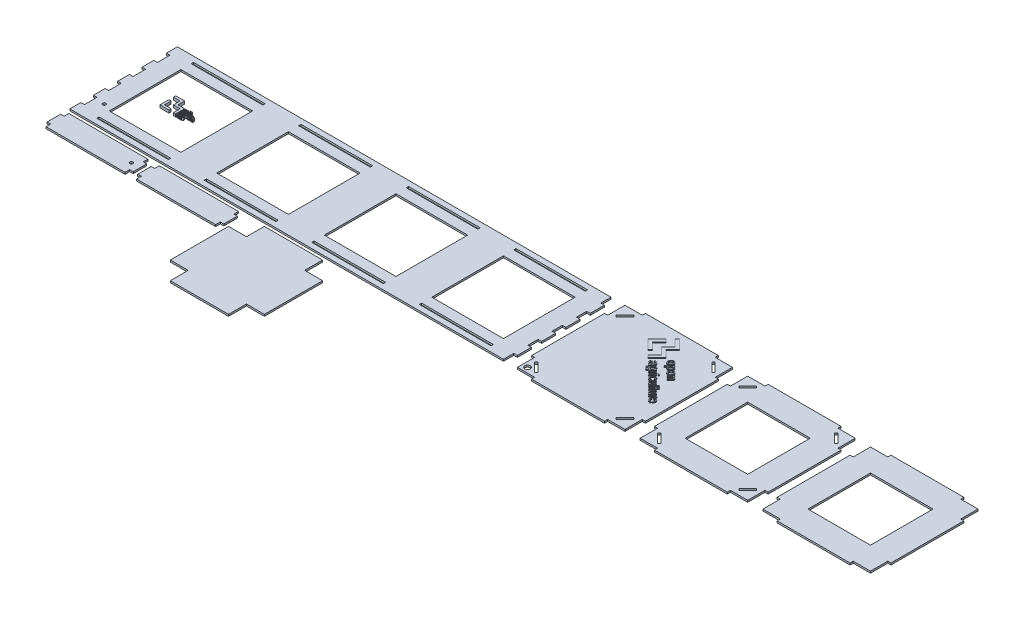
SolidWorks part; units mm, degrees
ref_plane "Front" through (0, 0, 0) normal (0, 0, 1) x (1, 0, 0)
ref_plane "Top" through (0, 0, 0) normal (0, 1, 0) x (1, 0, 0)
ref_plane "Right" through (0, 0, 0) normal (1, 0, 0) x (0, 0, -1)
sketch "Sketch1" plane through (0, 0, 0) normal (0, 1, 0) x (1, 0, 0)
  line L0 (0, 0) -> (228.6, 0) construction
  line L2 (-76.2, 76.2) -> (-76.2, -76.2) construction
  line L4 (76.2, 76.2) -> (76.2, -76.2) construction
  line L5 (-76.2, 76.2) -> (76.2, -76.2) construction
  line L6 (-76.2, -76.2) -> (76.2, 76.2) construction
  line L11 (76.2, 76.2) -> (228.6, 76.2)
  line L12 (76.2, 76.2) -> (76.2, -76.2) construction
  line L13 (76.2, -76.2) -> (228.6, -76.2)
  line L14 (228.6, 76.2) -> (228.6, -76.2) construction
  line L19 (-76.2, -76.2) -> (-228.6, -76.2)
  line L20 (-76.2, -76.2) -> (-76.2, 76.2) construction
  line L21 (-76.2, 76.2) -> (-228.6, 76.2)
  line L28 (76.2, -76.2) -> (-76.2, -76.2)
  line L34 (76.2, 76.2) -> (-76.2, 76.2)
  line L35 (-228.6, 76.2) -> (-228.6, -76.2) construction
  line L43 (-228.6, 76.2) -> (-381, 76.2)
  line L44 (-381, 76.2) -> (-381, -76.2) construction
  line L45 (-381, -76.2) -> (-228.6, -76.2)
  line L46 (228.6, 76.2) -> (228.6, 61.6712)
  line L47 (228.6, 61.6712) -> (233.68, 61.6712)
  line L48 (233.68, 61.6712) -> (233.68, 41.7322)
  line L49 (233.68, 41.7322) -> (228.6, 41.7322)
  line L50 (228.6, 41.7322) -> (228.6, 27.2034)
  line L51 (228.6, 27.2034) -> (233.68, 27.2034)
  line L63 (233.68, 27.2034) -> (233.68, 7.2644)
  line L64 (233.68, 7.2644) -> (228.6, 7.2644)
  line L65 (228.6, 7.2644) -> (228.6, -7.2644)
  line L66 (228.6, -7.2644) -> (233.68, -7.2644)
  line L67 (233.68, -7.2644) -> (233.68, -27.2034)
  line L68 (233.68, -27.2034) -> (228.6, -27.2034)
  line L69 (228.6, -27.2034) -> (228.6, -41.7322)
  line L70 (228.6, -41.7322) -> (233.68, -41.7322)
  line L71 (233.68, -41.7322) -> (233.68, -61.6712)
  line L72 (233.68, -61.6712) -> (228.6, -61.6712)
  line L73 (228.6, -61.6712) -> (228.6, -76.2)
  line L74 (-381, 76.2) -> (-386.08, 76.2)
  line L76 (-386.08, 60.5917) -> (-381, 60.5917)
  line L78 (-381, 42.8117) -> (-386.08, 42.8117)
  line L80 (-386.08, 26.1239) -> (-381, 26.1239)
  line L82 (-381, 8.3439) -> (-386.08, 8.3439)
  line L84 (-386.08, -8.3439) -> (-381, -8.3439)
  line L86 (-381, -26.1239) -> (-386.08, -26.1239)
  line L88 (-386.08, -42.8117) -> (-381, -42.8117)
  line L90 (-381, -60.5917) -> (-386.08, -60.5917)
  line L92 (-386.08, -76.2) -> (-381, -76.2)
  line L93 (233.68, 17.2339) -> (-381, 17.2339) construction
  line L94 (-381, 51.7017) -> (233.68, 51.7017) construction
  line L95 (-386.08, 76.2) -> (-386.08, 60.5917)
  line L96 (-386.08, 42.8117) -> (-386.08, 26.1239)
  line L97 (-381, 60.5917) -> (-381, 42.8117)
  line L98 (-381, 26.1239) -> (-381, 8.3439)
  line L99 (-381, -8.3439) -> (-381, -26.1239)
  line L100 (-381, -42.8117) -> (-381, -60.5917)
  line L101 (-381, -51.7017) -> (233.68, -51.7017) construction
  line L102 (-381, -17.2339) -> (233.68, -17.2339) construction
  line L103 (-386.08, 8.3439) -> (-386.08, -8.3439)
  line L104 (-386.08, -26.1239) -> (-386.08, -42.8117)
  line L105 (-386.08, -60.5917) -> (-386.08, -76.2)
  point P0 (0, 0)
  dimension "D1" = 152.4
  dimension "D2" = 152.4
  dimension "D3" = 5.08
  dimension "D4" = 19.939
  dimension "D5" = 17.78
extrude "Boss-Extrude1" add sketch "Sketch1" along normal blind 2.54
sketch "Sketch4" plane through (0, 2.54, 0) normal (0, 1, 0) x (1, 0, 0)
  line L0 (-228.6, 76.2) -> (-228.6, -76.2) construction
  line L1 (-228.6, 76.2) -> (-228.6, -76.2)
  line L2 (-76.2, 76.2) -> (-76.2, -76.2) construction
  line L3 (-76.2, 76.2) -> (-76.2, -76.2)
  line L4 (76.2, 76.2) -> (76.2, -76.2) construction
  line L5 (76.2, 76.2) -> (76.2, -76.2)
sketch "Sketch5" plane through (0, 2.54, 0) normal (0, 1, 0) x (1, 0, 0)
  line L0 (-381, -8.3439) -> (-381, 8.3439) construction
  line L1 (-228.6, 0) -> (-381, 0) construction
  line L2 (-228.6, 76.2) -> (-228.6, -76.2) construction
  line L3 (-228.6, 0) -> (-76.2, 0) construction
  line L4 (-76.2, 76.2) -> (-76.2, -76.2) construction
  line L5 (-76.2, 0) -> (76.2, 0) construction
  line L6 (76.2, 76.2) -> (76.2, -76.2) construction
  line L7 (76.2, 0) -> (228.6, 0) construction
  line L8 (228.6, -7.2644) -> (228.6, 7.2644) construction
  line L9 (-304.8, 0) -> (-304.8, -76.2) construction
  line L10 (-386.08, -76.2) -> (228.6, -76.2) construction
  line L11 (-152.4, 0) -> (-152.4, -76.2) construction
  line L12 (0, 0) -> (0, -76.2) construction
  line L13 (152.4, 0) -> (152.4, -76.2) construction
  line L14 (-254, -68.58) -> (-254, -76.2) construction
  line L15 (-355.6, -65.278) -> (-254, -65.278)
  line L16 (-355.6, -65.278) -> (-355.6, -68.58)
  line L17 (-355.6, -68.58) -> (-254, -68.58)
  line L18 (-254, -65.278) -> (-254, -68.58)
  line L19 (-355.6, -65.278) -> (-254, -68.58) construction
  line L20 (-355.6, -68.58) -> (-254, -65.278) construction
  line L21 (-203.2, -65.278) -> (-101.6, -65.278)
  line L22 (-203.2, -65.278) -> (-203.2, -68.58)
  line L23 (-203.2, -68.58) -> (-101.6, -68.58)
  line L24 (-101.6, -65.278) -> (-101.6, -68.58)
  line L25 (-203.2, -65.278) -> (-101.6, -68.58) construction
  line L26 (-203.2, -68.58) -> (-101.6, -65.278) construction
  line L27 (-50.8, -68.58) -> (50.8, -68.58)
  line L28 (-50.8, -68.58) -> (-50.8, -65.278)
  line L29 (-50.8, -65.278) -> (50.8, -65.278)
  line L30 (50.8, -68.58) -> (50.8, -65.278)
  line L31 (-50.8, -68.58) -> (50.8, -65.278) construction
  line L32 (-50.8, -65.278) -> (50.8, -68.58) construction
  line L33 (101.6, -68.58) -> (203.2, -68.58)
  line L34 (101.6, -68.58) -> (101.6, -65.278)
  line L35 (101.6, -65.278) -> (203.2, -65.278)
  line L36 (203.2, -68.58) -> (203.2, -65.278)
  line L37 (101.6, -68.58) -> (203.2, -65.278) construction
  line L38 (101.6, -65.278) -> (203.2, -68.58) construction
  line L39 (101.6, 65.278) -> (203.2, 68.58) construction
  line L40 (101.6, 68.58) -> (203.2, 65.278) construction
  line L41 (-50.8, 65.278) -> (50.8, 68.58) construction
  line L42 (-50.8, 68.58) -> (50.8, 65.278) construction
  line L43 (-203.2, 68.58) -> (-101.6, 65.278) construction
  line L44 (-203.2, 65.278) -> (-101.6, 68.58) construction
  line L45 (-355.6, 68.58) -> (-254, 65.278) construction
  line L46 (-355.6, 65.278) -> (-254, 68.58) construction
  line L47 (-254, 68.58) -> (-254, 76.2) construction
  line L48 (203.2, 68.58) -> (203.2, 65.278)
  line L49 (101.6, 65.278) -> (203.2, 65.278)
  line L50 (101.6, 68.58) -> (101.6, 65.278)
  line L51 (101.6, 68.58) -> (203.2, 68.58)
  line L52 (50.8, 68.58) -> (50.8, 65.278)
  line L53 (-50.8, 65.278) -> (50.8, 65.278)
  line L54 (-50.8, 68.58) -> (-50.8, 65.278)
  line L55 (-50.8, 68.58) -> (50.8, 68.58)
  line L56 (-101.6, 65.278) -> (-101.6, 68.58)
  line L57 (-203.2, 68.58) -> (-101.6, 68.58)
  line L58 (-203.2, 65.278) -> (-203.2, 68.58)
  line L59 (-203.2, 65.278) -> (-101.6, 65.278)
  line L60 (-254, 65.278) -> (-254, 68.58)
  line L61 (-355.6, 68.58) -> (-254, 68.58)
  line L62 (-355.6, 65.278) -> (-355.6, 68.58)
  line L63 (-355.6, 65.278) -> (-254, 65.278)
  line L65 (-355.6, 50.8) -> (-254, 50.8)
  line L66 (-355.6, 50.8) -> (-355.6, -50.8)
  line L67 (-355.6, -50.8) -> (-254, -50.8)
  line L68 (-254, 50.8) -> (-254, -50.8)
  line L69 (-355.6, 50.8) -> (-254, -50.8) construction
  line L70 (-355.6, -50.8) -> (-254, 50.8) construction
  line L71 (-203.2, 50.8) -> (-101.6, 50.8)
  line L72 (-203.2, 50.8) -> (-203.2, -50.8)
  line L73 (-203.2, -50.8) -> (-101.6, -50.8)
  line L74 (-101.6, 50.8) -> (-101.6, -50.8)
  line L75 (-203.2, 50.8) -> (-101.6, -50.8) construction
  line L76 (-203.2, -50.8) -> (-101.6, 50.8) construction
  line L77 (-50.8, 50.8) -> (50.8, 50.8)
  line L78 (-50.8, 50.8) -> (-50.8, -50.8)
  line L79 (-50.8, -50.8) -> (50.8, -50.8)
  line L80 (50.8, 50.8) -> (50.8, -50.8)
  line L81 (-50.8, 50.8) -> (50.8, -50.8) construction
  line L82 (-50.8, -50.8) -> (50.8, 50.8) construction
  line L83 (101.6, 50.8) -> (203.2, 50.8)
  line L84 (101.6, 50.8) -> (101.6, -50.8)
  line L85 (101.6, -50.8) -> (203.2, -50.8)
  line L86 (203.2, 50.8) -> (203.2, -50.8)
  line L87 (101.6, 50.8) -> (203.2, -50.8) construction
  line L88 (101.6, -50.8) -> (203.2, 50.8) construction
  circle A0 centre (-367.6, -45.8) radius 2.2225
  point P27 (-304.8, -66.929)
  point P32 (-152.4, -66.929)
  point P37 (0, -66.929)
  point P42 (152.4, -66.929)
  point P66 (152.4, 66.929)
  point P67 (0, 66.929)
  point P68 (-152.4, 66.929)
  point P69 (-304.8, 66.929)
  dimension "D5" = 4.445
  dimension "D7" = 5
  dimension "D1" = 7.62
  dimension "D2" = 3.302
  dimension "D3" = 101.6
  dimension "D4" = 101.6
  dimension "D6" = 12
extrude "Cut-Extrude2" cut sketch "Sketch5" against normal through all
sketch "Sketch6" plane through (0, 0, 0) normal (0, 1, 0) x (1, 0, 0)
  line L0 (0, 0) -> (324.5769, 0) construction
  line L1 (324.5769, 0) -> (324.5769, 78.4225) construction
  line L2 (248.3769, 76.2) -> (400.7769, 76.2) construction
  line L3 (248.3769, 76.2) -> (248.3769, -76.2) construction
  line L4 (248.3769, -76.2) -> (400.7769, -76.2) construction
  line L5 (400.7769, 76.2) -> (400.7769, -76.2) construction
  line L6 (248.3769, 76.2) -> (400.7769, -76.2) construction
  line L7 (248.3769, -76.2) -> (400.7769, 76.2) construction
  line L8 (324.5769, 0) -> (402.9994, 0) construction
  line L9 (324.5769, 0) -> (324.5769, -78.4225) construction
  line L10 (248.3769, 51.689) -> (248.3769, 76.2)
  line L11 (272.8879, 80.645) -> (376.2659, 80.645)
  line L12 (272.8879, 80.645) -> (272.8879, 76.2)
  line L13 (272.8879, 76.2) -> (376.2659, 76.2) construction
  line L14 (376.2659, 80.645) -> (376.2659, 76.2)
  line L15 (272.8879, 80.645) -> (376.2659, 76.2) construction
  line L16 (272.8879, 76.2) -> (376.2659, 80.645) construction
  line L17 (405.2219, -51.689) -> (400.7769, -51.689)
  line L18 (405.2219, -51.689) -> (405.2219, 51.689)
  line L19 (405.2219, 51.689) -> (400.7769, 51.689)
  line L20 (400.7769, -51.689) -> (400.7769, 51.689) construction
  line L21 (405.2219, -51.689) -> (400.7769, 51.689) construction
  line L22 (405.2219, 51.689) -> (400.7769, -51.689) construction
  line L23 (272.8879, -80.645) -> (376.2659, -80.645)
  line L24 (272.8879, -80.645) -> (272.8879, -76.2)
  line L25 (272.8879, -76.2) -> (376.2659, -76.2) construction
  line L26 (376.2659, -80.645) -> (376.2659, -76.2)
  line L27 (272.8879, -80.645) -> (376.2659, -76.2) construction
  line L28 (272.8879, -76.2) -> (376.2659, -80.645) construction
  line L29 (243.9319, 51.689) -> (248.3769, 51.689)
  line L30 (243.9319, 51.689) -> (243.9319, -51.689)
  line L31 (243.9319, -51.689) -> (248.3769, -51.689)
  line L32 (248.3769, 51.689) -> (248.3769, -51.689) construction
  line L33 (243.9319, 51.689) -> (248.3769, -51.689) construction
  line L34 (243.9319, -51.689) -> (248.3769, 51.689) construction
  line L35 (248.3769, 76.2) -> (272.8879, 76.2)
  line L36 (376.2659, 76.2) -> (400.7769, 76.2)
  line L37 (400.7769, 76.2) -> (400.7769, 51.689)
  line L38 (400.7769, -51.689) -> (400.7769, -76.2)
  line L39 (400.7769, -76.2) -> (376.2659, -76.2)
  line L40 (272.8879, -76.2) -> (248.3769, -76.2)
  line L41 (248.3769, -76.2) -> (248.3769, -51.689)
  line L42 (417.9219, 51.689) -> (417.9219, -51.689)
  line L43 (417.9219, 51.689) -> (422.3669, 51.689)
  line L44 (422.3669, 51.689) -> (422.3669, 76.2)
  line L45 (422.3669, 76.2) -> (446.8779, 76.2)
  line L46 (446.8779, 80.645) -> (446.8779, 76.2)
  line L47 (446.8779, 80.645) -> (550.2559, 80.645)
  line L48 (550.2559, 80.645) -> (550.2559, 76.2)
  line L49 (550.2559, 76.2) -> (574.7669, 76.2)
  line L50 (574.7669, 76.2) -> (574.7669, 51.689)
  line L51 (579.2119, 51.689) -> (574.7669, 51.689)
  line L52 (579.2119, -51.689) -> (579.2119, 51.689)
  line L53 (579.2119, -51.689) -> (574.7669, -51.689)
  line L54 (574.7669, -51.689) -> (574.7669, -76.2)
  line L55 (574.7669, -76.2) -> (550.2559, -76.2)
  line L56 (550.2559, -80.645) -> (550.2559, -76.2)
  line L57 (446.8779, -80.645) -> (550.2559, -80.645)
  line L58 (446.8779, -80.645) -> (446.8779, -76.2)
  line L59 (446.8779, -76.2) -> (422.3669, -76.2)
  line L60 (422.3669, -76.2) -> (422.3669, -51.689)
  line L61 (417.9219, -51.689) -> (422.3669, -51.689)
  line L62 (422.3669, 76.2) -> (574.7669, -76.2) construction
  line L63 (591.9119, 51.689) -> (591.9119, -51.689)
  line L64 (591.9119, 51.689) -> (596.3569, 51.689)
  line L65 (596.3569, 51.689) -> (596.3569, 76.2)
  line L66 (596.3569, 76.2) -> (620.8679, 76.2)
  line L67 (620.8679, 80.645) -> (620.8679, 76.2)
  line L68 (620.8679, 80.645) -> (724.2459, 80.645)
  line L69 (724.2459, 80.645) -> (724.2459, 76.2)
  line L70 (724.2459, 76.2) -> (748.7569, 76.2)
  line L71 (748.7569, 76.2) -> (748.7569, 51.689)
  line L72 (753.2019, 51.689) -> (748.7569, 51.689)
  line L73 (753.2019, -51.689) -> (753.2019, 51.689)
  line L74 (753.2019, -51.689) -> (748.7569, -51.689)
  line L75 (748.7569, -51.689) -> (748.7569, -76.2)
  line L76 (748.7569, -76.2) -> (724.2459, -76.2)
  line L77 (724.2459, -80.645) -> (724.2459, -76.2)
  line L78 (620.8679, -80.645) -> (724.2459, -80.645)
  line L79 (620.8679, -80.645) -> (620.8679, -76.2)
  line L80 (620.8679, -76.2) -> (596.3569, -76.2)
  line L81 (596.3569, -76.2) -> (596.3569, -51.689)
  line L82 (591.9119, -51.689) -> (596.3569, -51.689)
  line L83 (596.3569, 76.2) -> (748.7569, -76.2) construction
  line L84 (454.2439, 44.323) -> (542.8899, 44.323)
  line L85 (454.2439, 44.323) -> (454.2439, -44.323)
  line L86 (454.2439, -44.323) -> (542.8899, -44.323)
  line L87 (542.8899, 44.323) -> (542.8899, -44.323)
  line L88 (454.2439, 44.323) -> (542.8899, -44.323) construction
  line L89 (454.2439, -44.323) -> (542.8899, 44.323) construction
  line L91 (716.8799, 44.323) -> (628.2339, 44.323)
  line L92 (716.8799, 44.323) -> (716.8799, -44.323)
  line L93 (716.8799, -44.323) -> (628.2339, -44.323)
  line L94 (628.2339, 44.323) -> (628.2339, -44.323)
  line L95 (716.8799, 44.323) -> (628.2339, -44.323) construction
  line L96 (716.8799, -44.323) -> (628.2339, 44.323) construction
  point P22 (246.1544, 0)
  point P67 (498.5669, 0)
  point P72 (672.5569, 0)
  dimension "D1" = 152.4
  dimension "D2" = 152.4
  dimension "D3" = 4.445
  dimension "D4" = 103.378
  dimension "D5" = 324.5769
  dimension "D7" = 12.7
  dimension "D8" = 88.646
  dimension "D6" = 3
extrude "Boss-Extrude2" add sketch "Sketch6" along normal blind 2.54 separate body
sketch "Sketch7" plane through (0, 0, 0) normal (0, 1, 0) x (1, 0, 0)
  line L0 (-355.6, 65.278) -> (-355.6, -46.736) construction
  line L1 (-381.08, -82.55) -> (-269.066, -82.55)
  line L2 (-381.08, -82.55) -> (-381.08, -89.2175)
  line L3 (-381.08, -114.935) -> (-269.066, -114.935)
  line L4 (-269.066, -82.55) -> (-269.066, -89.2175)
  line L5 (-381.08, -82.55) -> (-269.066, -114.935) construction
  line L6 (-381.08, -114.935) -> (-269.066, -82.55) construction
  line L7 (-355.6, 50.8) -> (-355.6, -50.8) construction
  line L8 (-355.6, -46.736) -> (-355.6, -50.8) construction
  line L9 (248.3769, -51.689) -> (248.3769, -76.2) construction
  line L10 (248.3769, -76.2) -> (272.8879, -76.2) construction
  line L12 (-381.08, -89.2175) -> (-386.08, -89.2175)
  line L13 (256.6811, -55.3235) -> (269.2534, -67.8958) construction
  line L14 (256.6811, -55.3235) -> (254.3462, -57.6583) construction
  line L15 (254.3462, -57.6583) -> (266.9186, -70.2307) construction
  line L16 (269.2534, -67.8958) -> (266.9186, -70.2307) construction
  line L17 (256.6811, -55.3235) -> (266.9186, -70.2307) construction
  line L18 (254.3462, -57.6583) -> (269.2534, -67.8958) construction
  line L19 (-386.08, -89.2175) -> (-386.08, -108.2675)
  line L20 (-386.08, -108.2675) -> (-381.08, -108.2675)
  line L21 (248.3769, -51.689) -> (272.8879, -76.2) construction
  line L22 (261.7998, -62.7771) -> (260.6324, -63.9445) construction
  line L23 (-381.08, -108.2675) -> (-381.08, -114.935)
  line L24 (-269.066, -89.2175) -> (-264.066, -89.2175)
  line L25 (-264.066, -89.2175) -> (-264.066, -108.2675)
  line L26 (-264.066, -108.2675) -> (-269.066, -108.2675)
  line L27 (-269.066, -108.2675) -> (-269.066, -114.935)
  line L28 (-386.08, -76.2) -> (228.6, -76.2) construction
  line L29 (-386.08, -60.5917) -> (-386.08, -76.2) construction
  line L30 (-252.716, -82.55) -> (-140.702, -82.55)
  line L31 (-252.716, -82.55) -> (-252.716, -89.2175)
  line L32 (-252.716, -114.935) -> (-140.702, -114.935)
  line L33 (-140.702, -82.55) -> (-140.702, -89.2175)
  line L34 (-252.716, -89.2175) -> (-257.716, -89.2175)
  line L35 (-257.716, -89.2175) -> (-257.716, -108.2675)
  line L36 (-257.716, -108.2675) -> (-252.716, -108.2675)
  line L37 (-252.716, -108.2675) -> (-252.716, -114.935)
  line L38 (-140.702, -89.2175) -> (-135.702, -89.2175)
  line L39 (-135.702, -89.2175) -> (-135.702, -108.2675)
  line L40 (-135.702, -108.2675) -> (-140.702, -108.2675)
  line L41 (-140.702, -108.2675) -> (-140.702, -114.935)
  line L42 (-252.716, -82.55) -> (-140.702, -114.935) construction
  line L43 (-252.716, -114.935) -> (-140.702, -82.55) construction
  point P0 (-325.073, -98.7425)
  point P14 (261.7998, -62.7771)
  point P38 (-196.709, -98.7425)
  dimension "D1" = 32.385
  dimension "D2" = 4.064
  dimension "D3" = 3.302
  dimension "D4" = 19.05
  dimension "D5" = 17.78
  dimension "D6" = 5
  dimension "D7" = 6.35
  dimension "D9" = 6.35
  dimension "D8" = 2
extrude "Boss-Extrude3" add sketch "Sketch7" along normal blind 2.54 separate body
sketch "Sketch8" plane through (0, 2.54, 0) normal (0, 1, 0) x (1, 0, 0)
  line L0 (254.3462, -57.6583) -> (266.9186, -70.2307) construction
  line L1 (269.2534, -67.8958) -> (266.9186, -70.2307) construction
  line L2 (256.6811, -55.3235) -> (269.2534, -67.8958) construction
  line L3 (256.6811, -55.3235) -> (254.3462, -57.6583) construction
  line L4 (254.3462, -57.6583) -> (266.9186, -70.2307)
  line L5 (269.2534, -67.8958) -> (266.9186, -70.2307)
  line L6 (256.6811, -55.3235) -> (269.2534, -67.8958)
  line L7 (256.6811, -55.3235) -> (254.3462, -57.6583)
  line L8 (248.3769, 76.2) -> (400.7769, -76.2) construction
  line L9 (269.2534, 67.8958) -> (256.6811, 55.3235)
  line L10 (269.2534, 67.8958) -> (266.9186, 70.2307)
  line L11 (266.9186, 70.2307) -> (254.3462, 57.6583)
  line L12 (256.6811, 55.3235) -> (254.3462, 57.6583)
  line L13 (392.4727, 55.3235) -> (379.9003, 67.8958)
  line L14 (392.4727, 55.3235) -> (394.8076, 57.6583)
  line L15 (394.8076, 57.6583) -> (382.2352, 70.2307)
  line L16 (379.9003, 67.8958) -> (382.2352, 70.2307)
  line L17 (379.9003, -67.8958) -> (392.4727, -55.3235)
  line L18 (379.9003, -67.8958) -> (382.2352, -70.2307)
  line L19 (382.2352, -70.2307) -> (394.8076, -57.6583)
  line L20 (392.4727, -55.3235) -> (394.8076, -57.6583)
  line L21 (422.3669, -51.689) -> (446.8779, -76.2) construction
  line L22 (428.3362, -57.6583) -> (430.6711, -55.3235)
  line L23 (430.6711, -55.3235) -> (443.2434, -67.8958)
  line L24 (443.2434, -67.8958) -> (440.9086, -70.2307)
  line L25 (434.6224, -63.9445) -> (436.9573, -61.6096) construction
  line L26 (428.3362, -57.6583) -> (440.9086, -70.2307)
  line L27 (422.3669, 76.2) -> (574.7669, -76.2) construction
  line L28 (430.6711, 55.3235) -> (428.3362, 57.6583)
  line L29 (440.9086, 70.2307) -> (428.3362, 57.6583)
  line L30 (440.9086, 70.2307) -> (443.2434, 67.8958)
  line L31 (443.2434, 67.8958) -> (430.6711, 55.3235)
  line L32 (553.8903, 67.8958) -> (556.2252, 70.2307)
  line L33 (568.7976, 57.6583) -> (556.2252, 70.2307)
  line L34 (568.7976, 57.6583) -> (566.4627, 55.3235)
  line L35 (566.4627, 55.3235) -> (553.8903, 67.8958)
  line L36 (566.4627, -55.3235) -> (568.7976, -57.6583)
  line L37 (556.2252, -70.2307) -> (568.7976, -57.6583)
  line L38 (556.2252, -70.2307) -> (553.8903, -67.8958)
  line L39 (553.8903, -67.8958) -> (566.4627, -55.3235)
  circle A0 centre (324.5769, 0) radius 20.7898 construction
  circle A1 centre (324.5769, 0) radius 20.7898 construction
  circle A2 centre (324.5769, 0) radius 20.7898 construction
  circle A3 centre (324.5769, 0) radius 20.7898 construction
  circle A4 centre (498.5669, 0) radius 62.6822 construction
  point P28 (324.5769, 0)
  point P58 (498.5669, 0)
  dimension "D1" = 4
  dimension "D2" = 4
extrude "Cut-Extrude3" cut sketch "Sketch8" against normal through all
sketch "Sketch10" plane through (0, 2.54, 0) normal (0, 1, 0) x (1, 0, 0)
  line L0 (-254, 50.8) -> (-355.6, 50.8) construction
  line L1 (-101.6, 50.8) -> (-203.2, 50.8) construction
  line L2 (50.8, 50.8) -> (-50.8, 50.8) construction
  line L3 (203.2, 50.8) -> (101.6, 50.8) construction
  line L4 (-294.64, 50.8) -> (-314.96, 50.8)
  line L5 (-142.24, 50.8) -> (-162.56, 50.8)
  line L6 (10.16, 50.8) -> (-10.16, 50.8)
  line L7 (162.56, 50.8) -> (142.24, 50.8)
  line L8 (-355.6, -45.8) -> (-254, -45.8)
  line L9 (-304.8, -45.8) -> (-304.8, -50.8) construction
  line L14 (-355.6, 50.8) -> (-355.6, -50.8) construction
  line L15 (-254, -50.8) -> (-254, 50.8) construction
  line L16 (-355.6, -50.8) -> (-254, -50.8) construction
  line L17 (-203.2, -45.8) -> (-101.6, -45.8)
  line L18 (-203.2, 50.8) -> (-203.2, -50.8) construction
  line L19 (-101.6, -50.8) -> (-101.6, 50.8) construction
  line L20 (-50.8, -45.8) -> (50.8, -45.8)
  line L21 (-50.8, 50.8) -> (-50.8, -50.8) construction
  line L22 (50.8, -50.8) -> (50.8, 50.8) construction
  line L23 (101.6, -45.8) -> (203.2, -45.8)
  line L24 (101.6, 50.8) -> (101.6, -50.8) construction
  line L25 (203.2, -50.8) -> (203.2, 50.8) construction
  line L26 (-264.066, -89.2175) -> (-269.066, -89.2175) construction
  arc A0 (-314.96, 50.8) -> (-294.64, 50.8) centre (-304.8, 50.8) ccw
  arc A1 (-162.56, 50.8) -> (-142.24, 50.8) centre (-152.4, 50.8) ccw
  arc A2 (-10.16, 50.8) -> (10.16, 50.8) centre (0, 50.8) ccw
  arc A3 (142.24, 50.8) -> (162.56, 50.8) centre (152.4, 50.8) ccw
  dimension "D1" = 20.32
sketch "Sketch11" plane through (0, 0, 0) normal (0, 1, 0) x (1, 0, 0)
  line L0 (-203.2, -50.8) -> (-203.2, -65.278) construction
  line L5 (-103.952, -107.95) -> (-21.402, -107.95) construction
  line L6 (-103.952, -107.95) -> (-103.952, -190.5) construction
  line L7 (-103.952, -190.5) -> (-21.402, -190.5) construction
  line L8 (-21.402, -107.95) -> (-21.402, -190.5) construction
  line L9 (-103.952, -107.95) -> (-21.402, -190.5) construction
  line L10 (-103.952, -190.5) -> (-21.402, -107.95) construction
  line L11 (-103.952, -107.95) -> (-129.352, -107.95)
  line L12 (-129.352, -107.95) -> (-129.352, -190.5)
  line L13 (-129.352, -190.5) -> (-103.952, -190.5)
  line L14 (-103.952, -107.95) -> (-103.952, -82.55)
  line L15 (-103.952, -82.55) -> (-21.402, -82.55)
  line L16 (-21.402, -82.55) -> (-21.402, -107.95)
  line L17 (-21.402, -107.95) -> (3.998, -107.95)
  line L18 (3.998, -107.95) -> (3.998, -190.5)
  line L19 (3.998, -190.5) -> (-21.402, -190.5)
  line L20 (-21.402, -190.5) -> (-21.402, -215.9)
  line L21 (-21.402, -215.9) -> (-103.952, -215.9)
  line L22 (-103.952, -215.9) -> (-103.952, -190.5)
  line L23 (-386.08, -76.2) -> (228.6, -76.2) construction
  line L24 (-135.702, -108.2675) -> (-135.702, -89.2175) construction
  point P0 (-62.677, -149.225)
  dimension "D1" = 82.55
  dimension "D2" = 82.55
  dimension "D3" = 25.4
  dimension "D4" = 6.35
  dimension "D5" = 6.35
extrude "Boss-Extrude5" add sketch "Sketch11" along normal blind 2.54 separate body
sketch "Sketch12" plane through (0, 2.54, 0) normal (0, 1, 0) x (1, 0, 0)
  line L0 (-103.952, -107.95) -> (-21.402, -107.95)
  line L1 (-21.402, -107.95) -> (-21.402, -190.5)
  line L2 (-21.402, -190.5) -> (-103.952, -190.5)
  line L3 (-103.952, -107.95) -> (-103.952, -190.5)
sketch "Sketch13" plane through (0, 0, 0) normal (0, 1, 0) x (1, 0, 0)
  line L16 (-325.8728, 13.6053) -> (-313.1082, 13.6053)
  line L17 (-313.1082, 13.6053) -> (-313.1082, 4.1223)
  line L18 (-313.1082, 4.1223) -> (-303.6478, 4.1223)
  line L19 (330.1215, 72.0796) -> (343.0158, 59.1854)
  line L20 (343.0158, 59.1854) -> (333.4365, 49.6061)
  line L21 (333.4365, 49.6061) -> (342.9929, 40.0497)
  line L22 (342.9929, 40.0497) -> (330.0758, 27.1326)
  line L24 (326.8522, 30.3562) -> (336.5001, 40.004)
  line L25 (336.5001, 40.004) -> (326.9665, 49.5375)
  line L26 (326.9665, 49.5375) -> (336.5915, 59.1625)
  line L27 (336.5915, 59.1625) -> (326.898, 68.856)
  line L28 (326.898, 68.856) -> (330.1215, 72.0796)
  line L29 (320.5423, 62.5004) -> (323.7887, 59.2539)
  line L30 (323.7887, 59.2539) -> (314.118, 49.5832)
  line L31 (314.118, 49.5832) -> (323.7658, 39.9354)
  line L32 (323.7658, 39.9354) -> (320.5194, 36.689)
  line L33 (320.5194, 36.689) -> (307.6252, 49.5832)
  line L34 (307.6252, 49.5832) -> (320.5423, 62.5004)
  line L36 (330.9952, 27.004) -> (384.8992, -26.9) construction
  line L37 (346.6958, 37.2946) -> (422.1745, -38.1841) construction
  line L38 (326.8522, 30.3562) -> (330.0758, 27.1326)
  line L41 (-303.6478, 4.1223) -> (-303.6478, -8.665)
  line L43 (-306.839, -8.665) -> (-306.839, 0.8859)
  line L44 (-306.839, 0.8859) -> (-316.2767, 0.8859)
  line L45 (-316.2767, 0.8859) -> (-316.2767, 10.4141)
  line L46 (-316.2767, 10.4141) -> (-325.8728, 10.4141)
  line L47 (-325.8728, 10.4141) -> (-325.8728, 13.6053)
  line L48 (-325.8728, 4.1223) -> (-322.659, 4.1223)
  line L49 (-322.659, 4.1223) -> (-322.659, -5.4512)
  line L50 (-322.659, -5.4512) -> (-313.1082, -5.4512)
  line L51 (-313.1082, -5.4512) -> (-313.1082, -8.665)
  line L52 (-313.1082, -8.665) -> (-325.8728, -8.665)
  line L53 (-325.8728, -8.665) -> (-325.8728, 4.1223)
  line L54 (-302.7825, -8.6643) -> (-251.1165, -8.6643) construction
  line L55 (-355.6, 50.8) -> (-254, -45.8) construction
  line L56 (-306.839, -8.665) -> (-303.6478, -8.665)
  line L57 (-302.7825, -8.6643) -> (-302.7825, 4.1223) construction
  line L58 (-302.7825, 4.1223) -> (-303.6478, 4.1223) construction
  line L59 (-302.7825, 0.8859) -> (-284.89, 0.8859) construction
  line L60 (-302.7825, -3.412) -> (-283.4069, -3.412) construction
  line L61 (-355.6, 50.8) -> (-355.6, -50.8) construction
  line L62 (-279.4, 25.4) -> (-330.2, 25.4) construction
  line L63 (-279.4, 25.4) -> (-279.4, -20.4) construction
  line L64 (-279.4, -20.4) -> (-330.2, -20.4) construction
  line L65 (-330.2, 25.4) -> (-330.2, -20.4) construction
  line L66 (-279.4, 25.4) -> (-330.2, -20.4) construction
  line L67 (-279.4, -20.4) -> (-330.2, 25.4) construction
  line L68 (-254, 50.8) -> (-355.6, 50.8) construction
  line L69 (-355.6, -45.8) -> (-254, -45.8) construction
  line L70 (-254, -50.8) -> (-254, 50.8) construction
  text T0 "mit" font "Arial" height in points 18
  text T1 "media" font "Arial" height in points 18
  text T2 "lab" font "Arial" height in points 18
  text T3 "open" font "Arial" height in points 44
  text T4 " agriculture" font "Arial" height in points 44
  point P56 (-296.666, 3.4026)
  dimension "D1" = 25.4
  dimension "D2" = 31.75
  dimension "D4" = 25.4
  dimension "D5" = 25.4
  dimension "D6" = 25.4
sketch "Sketch14" plane through (0, 2.54, 0) normal (0, 1, 0) x (1, 0, 0)
  line L0 (-264.066, -98.7425) -> (-276.2885, -98.7425) construction
  line L1 (-264.066, -108.2675) -> (-264.066, -89.2175) construction
  circle A0 centre (-276.2885, -98.7425) radius 2.2225
  circle A1 centre (-367.6, -45.8) radius 2.2225 construction
  dimension "D1" = 10
extrude "Cut-Extrude4" cut sketch "Sketch14" against normal through all
extrude "Boss-Extrude7" add sketch "Sketch13" along normal blind 3.81 separate body
sketch "Sketch15" plane through (0, 2.54, 0) normal (0, 1, 0) x (1, 0, 0)
  line L0 (248.3769, -76.2) -> (260.6324, -63.9445) construction
  line L1 (254.3462, -57.6583) -> (266.9186, -70.2307) construction
  line L2 (255.556, -75.1169) -> (255.556, -76.2) construction
  line L3 (248.3769, -76.2) -> (272.8879, -76.2) construction
  line L4 (260.6324, -63.9445) -> (259.8665, -64.7104) construction
  line L5 (248.3769, 76.2) -> (400.7769, -76.2) construction
  circle A0 centre (255.556, -69.0209) radius 3.8725
  circle A1 centre (255.556, -69.0209) radius 6.096 construction
  dimension "D1" = 7.745
  dimension "D2" = 12.192
extrude "Cut-Extrude5" cut sketch "Sketch15" against normal through all
sketch "Sketch16" plane through (0, 2.54, 0) normal (0, 1, 0) x (1, 0, 0)
  line L0 (454.2439, 44.323) -> (454.2439, -44.323) construction
  line L1 (466.9439, 9.398) -> (494.3251, 9.398) construction
  line L2 (466.9439, 31.623) -> (511.3939, 31.623)
  line L3 (466.9439, 31.623) -> (466.9439, -12.827)
  line L4 (466.9439, -12.827) -> (511.3939, -12.827)
  line L6 (466.9439, 31.623) -> (511.3939, -12.827) construction
  line L7 (466.9439, -12.827) -> (511.3939, 31.623) construction
  line L8 (494.3251, 9.398) -> (489.1689, 9.398) construction
  line L9 (511.3939, 31.623) -> (511.3939, 11.5554)
  line L10 (517.654, 18.3681) -> (516.6571, 21.1073)
  line L11 (489.1689, 31.623) -> (489.1689, -12.827) construction
  line L12 (501.8689, 16.7005) -> (492.4709, 16.7005)
  line L13 (501.8689, 2.0955) -> (492.4709, 2.0955)
  line L14 (489.1689, 16.7005) -> (489.1689, 2.0955) construction
  line L15 (514.5689, 16.7005) -> (489.1689, 16.7005) construction
  line L16 (514.5689, 2.0955) -> (489.1689, 2.0955) construction
  line L17 (505.4378, 15.6027) -> (512.353, 10.9037)
  line L18 (514.5689, 9.398) -> (513.9111, 9.398) construction
  line L19 (514.5689, 9.398) -> (489.1689, 9.398) construction
  line L20 (538.0059, 9.398) -> (513.9111, 9.398) construction
  line L21 (501.8689, 16.7005) -> (501.8689, 2.0955) construction
  line L22 (511.3939, -4.7879) -> (511.3939, -12.827)
  line L23 (542.8899, 44.323) -> (454.2439, 44.323) construction
  line L24 (489.1689, 20.0025) -> (489.1689, 20.5105) construction
  line L25 (489.1689, -1.2065) -> (489.1689, -1.7145) construction
  line L26 (489.1689, 20.0025) -> (489.1689, -1.2065)
  arc A1 (514.8515, 7.5248) -> (521.2219, 15.7408) centre (520.9189, 9.398) ccw
  arc A2 (507.0303, -0.5555) -> (520.2621, 26.4724) centre (520.9189, 9.398) ccw
  arc A3 (520.2621, 26.4724) -> (516.6571, 21.1073) centre (520.4158, 22.4753) ccw
  arc A4 (517.654, 18.3681) -> (521.2219, 15.7408) centre (521.4128, 19.7362) ccw
  arc A5 (505.4378, 15.6027) -> (501.8689, 16.7005) centre (501.8689, 10.3505) ccw
  arc A6 (507.0303, -0.5555) -> (501.8689, 2.0955) centre (501.8689, -4.2545) ccw
  arc A7 (514.8515, 7.5248) -> (512.353, 10.9037) centre (508.7841, 5.6516) ccw
  arc A8 (492.4709, 2.0955) -> (489.1689, -1.2065) centre (492.4709, -1.2065) ccw
  arc A9 (489.1689, 20.0025) -> (492.4709, 16.7005) centre (492.4709, 20.0025) ccw
  point P4 (489.1689, 9.398)
  point P28 (515.0748, 25.4545)
  dimension "D7" = 4
  dimension "D8" = 6.35
  dimension "D9" = 6.35
  dimension "D10" = 6.35
  dimension "D12" = 12.7
  dimension "D17" = 3.302
  dimension "D1" = 44.45
  dimension "D2" = 44.45
  dimension "D3" = 12.7
  dimension "D4" = 7.3025
  dimension "D6" = 20
  dimension "D11" = 31.75
  dimension "D13" = 12.7
  dimension "D14" = 12.7
  dimension "D15" = 3.81
  dimension "D16" = 3.81
  dimension "D5" = 7.3025
sketch "Sketch17" plane through (0, 2.54, 0) normal (0, 1, 0) x (1, 0, 0)
  line L0 (511.3939, -4.7879) -> (511.3939, -12.827) construction
  line L1 (466.9439, -12.827) -> (511.3939, -12.827) construction
  line L2 (466.9439, 31.623) -> (466.9439, -12.827) construction
  line L3 (466.9439, 31.623) -> (511.3939, 31.623) construction
  line L4 (511.3939, 31.623) -> (511.3939, 11.5554) construction
  line L5 (511.3939, -4.7879) -> (511.3939, -12.827)
  line L6 (466.9439, -12.827) -> (511.3939, -12.827)
  line L7 (466.9439, 31.623) -> (466.9439, -12.827)
  line L8 (466.9439, 31.623) -> (511.3939, 31.623)
  line L9 (511.3939, 31.623) -> (511.3939, 11.5554)
  line L10 (501.8689, 16.7005) -> (492.4709, 16.7005) construction
  line L11 (505.4378, 15.6027) -> (512.353, 10.9037) construction
  line L12 (517.654, 18.3681) -> (516.6571, 21.1073) construction
  line L13 (501.8689, 2.0955) -> (492.4709, 2.0955) construction
  line L14 (501.8689, 16.7005) -> (492.4709, 16.7005)
  line L15 (505.4378, 15.6027) -> (512.353, 10.9037)
  line L16 (517.654, 18.3681) -> (516.6571, 21.1073)
  line L17 (501.8689, 2.0955) -> (492.4709, 2.0955)
  arc A0 (489.1689, 20.0025) -> (492.4709, 16.7005) centre (492.4709, 20.0025) ccw construction
  arc A1 (505.4378, 15.6027) -> (501.8689, 16.7005) centre (501.8689, 10.3505) ccw construction
  arc A2 (514.8515, 7.5248) -> (512.353, 10.9037) centre (508.7841, 5.6516) ccw construction
  arc A3 (520.2621, 26.4724) -> (516.6571, 21.1073) centre (520.4158, 22.4753) ccw construction
  arc A4 (517.654, 18.3681) -> (521.2219, 15.7408) centre (521.4128, 19.7362) ccw construction
  arc A5 (514.8515, 7.5248) -> (521.2219, 15.7408) centre (520.9189, 9.398) ccw construction
  arc A6 (507.0303, -0.5555) -> (520.2621, 26.4724) centre (520.9189, 9.398) ccw construction
  arc A7 (507.0303, -0.5555) -> (501.8689, 2.0955) centre (501.8689, -4.2545) ccw construction
  arc A8 (492.4709, 2.0955) -> (489.1689, -1.2065) centre (492.4709, -1.2065) ccw construction
  arc A9 (489.1689, 20.0025) -> (492.4709, 16.7005) centre (492.4709, 20.0025) ccw
  arc A10 (505.4378, 15.6027) -> (501.8689, 16.7005) centre (501.8689, 10.3505) ccw
  arc A11 (514.8515, 7.5248) -> (512.353, 10.9037) centre (508.7841, 5.6516) ccw
  arc A12 (520.2621, 26.4724) -> (516.6571, 21.1073) centre (520.4158, 22.4753) ccw
  arc A13 (517.654, 18.3681) -> (521.2219, 15.7408) centre (521.4128, 19.7362) ccw
  arc A14 (514.8515, 7.5248) -> (521.2219, 15.7408) centre (520.9189, 9.398) ccw
  arc A15 (507.0303, -0.5555) -> (520.2621, 26.4724) centre (520.9189, 9.398) ccw
  arc A16 (507.0303, -0.5555) -> (501.8689, 2.0955) centre (501.8689, -4.2545) ccw
  arc A17 (492.4709, 2.0955) -> (489.1689, -1.2065) centre (492.4709, -1.2065) ccw
sketch "Sketch18" plane through (0, 2.54, 0) normal (0, 1, 0) x (1, 0, 0)
  line L0 (489.1689, 20.0025) -> (489.1689, -1.2065)
